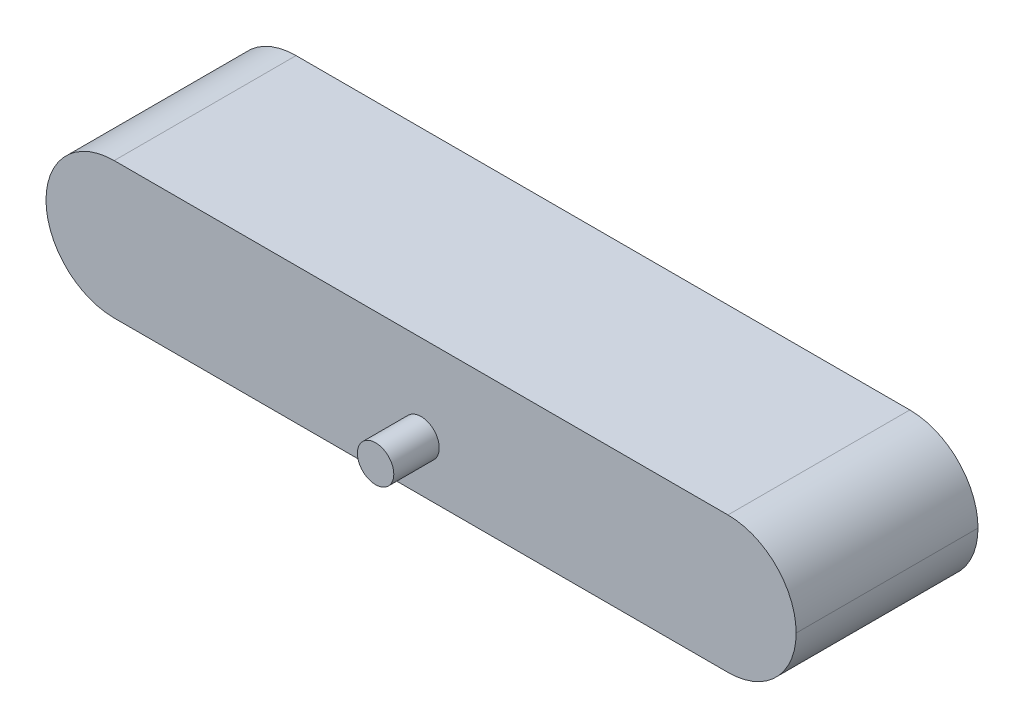
SolidWorks part; units mm, degrees
ref_plane "Front Plane" through (0, 0, 0) normal (0, 0, 1) x (1, 0, 0)
ref_plane "Top Plane" through (0, 0, 0) normal (0, 1, 0) x (1, 0, 0)
ref_plane "Right Plane" through (0, 0, 0) normal (1, 0, 0) x (0, 0, -1)
sketch "Sketch1" plane through (0, 0, 0) normal (0, 0, 1) x (1, 0, 0)
  line L1 (82.5, -15) -> (-82.5, -15)
  line L2 (82.5, -15) -> (82.5, 15)
  line L3 (82.5, 15) -> (-82.5, 15)
  line L4 (-82.5, -15) -> (-82.5, 15)
  line L5 (82.5, -15) -> (-82.5, 15) construction
  line L6 (82.5, 15) -> (-82.5, -15) construction
  point P0 (0, 0)
  dimension "D1" = 30
  dimension "D2" = 165
extrude "Boss-Extrude1" add sketch "Sketch1" along normal blind 40
fillet "Fillet1" radius 15 4 edges at (-82.5, 15, 20) (82.5, -15, 20) (-82.5, -15, 20) (82.5, 15, 20)
sketch "Sketch2" plane through (0, -15, 0) normal (0, -1, 0) x (1, 0, 0)
  line L0 (-67.5, 0) -> (67.5, 0) construction
  line L1 (13, 7) -> (-13, 7)
  line L2 (13, 7) -> (13, 14)
  line L3 (13, 14) -> (-13, 14)
  line L4 (-13, 7) -> (-13, 14)
  line L5 (13, 7) -> (-13, 14) construction
  line L6 (13, 14) -> (-13, 7) construction
  point P0 (0, 10.5)
  point P5 (0, 0)
  dimension "D1" = 7
  dimension "D2" = 26
  dimension "D3" = 7
extrude "Boss-Extrude2" add sketch "Sketch2" along normal blind 6
sketch "Sketch3" plane through (0, 0, 40) normal (0, 0, 1) x (1, 0, 0)
  line L0 (67.5, 15) -> (-67.5, 15) construction
  circle A0 centre (0, -4) radius 4
  dimension "D1" = 8
  dimension "D2" = 19
extrude "Boss-Extrude3" add sketch "Sketch3" along normal blind 10
